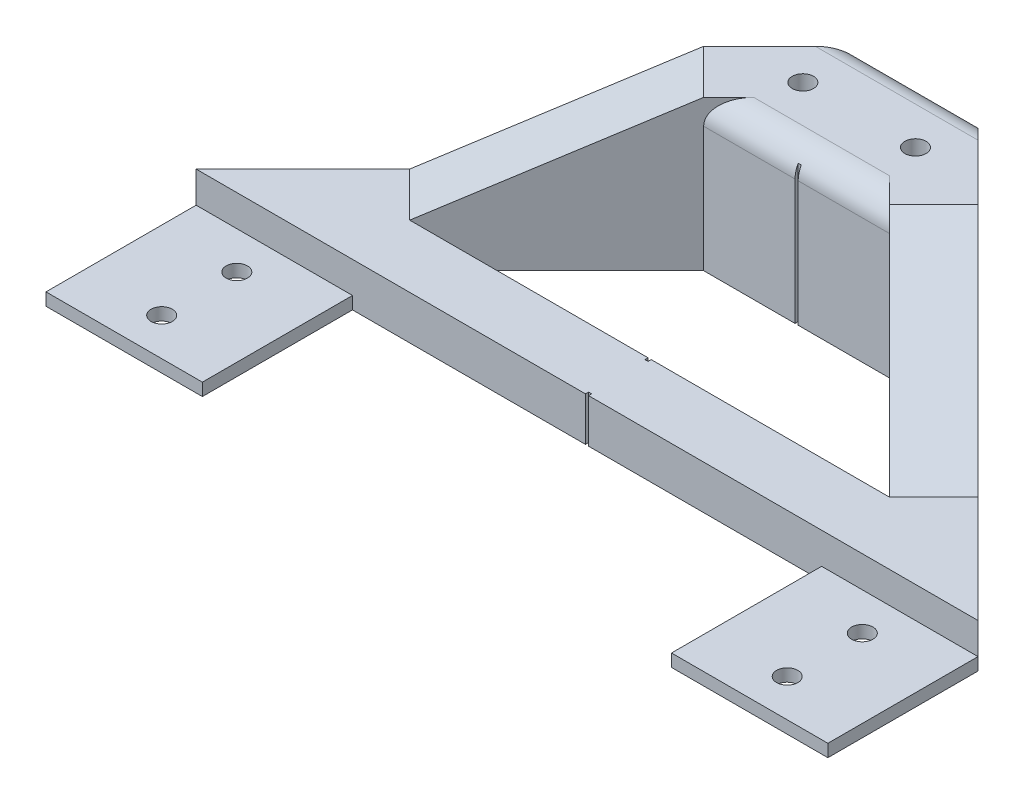
SolidWorks part; units mm, degrees
ref_plane "Front Plane" through (0, 0, 0) normal (0, 0, 1) x (1, 0, 0)
ref_plane "Top Plane" through (0, 0, 0) normal (0, 1, 0) x (1, 0, 0)
ref_plane "Right Plane" through (0, 0, 0) normal (1, 0, 0) x (0, 0, -1)
sketch "Triangle" plane through (0, 0, 0) normal (0, 1, 0) x (1, 0, 0)
  line L0 (0, 0) -> (125, 0)
  line L1 (125, 0) -> (71.5, 53.5)
  line L2 (53.5, 53.5) -> (0, 0)
  line L3 (62.5, 0) -> (62.5, 53.5) construction
  line L4 (53.5, 53.5) -> (71.5, 53.5)
  line L5 (24.1421, 10) -> (100.8579, 10)
  line L6 (100.8579, 10) -> (77.3579, 33.5)
  line L7 (77.3579, 33.5) -> (47.6421, 33.5)
  line L8 (47.6421, 33.5) -> (24.1421, 10)
  dimension "D1" = 125
  dimension "D2" = 20
  dimension "D3" = 45
  dimension "D4" = 45
  dimension "D5" = 10
  dimension "D6" = 18
  dimension "D7" = 10
  dimension "D8" = 45
  dimension "D9" = 10
  dimension "D10" = 45
sketch "Bearing Mounts" plane through (0, 0, 0) normal (0, 1, 0) x (1, 0, 0)
  line L0 (12.5, -24) -> (12.5, 0) construction
  line L1 (25, 0) -> (0, 0)
  line L2 (25, 0) -> (25, -24)
  line L3 (25, -24) -> (0, -24)
  line L4 (0, 0) -> (0, -24)
  line L5 (112.5, -24) -> (112.5, 0) construction
  line L6 (125, 0) -> (100, 0)
  line L7 (125, 0) -> (125, -24)
  line L8 (125, -24) -> (100, -24)
  line L9 (100, 0) -> (100, -24)
  line L10 (100, -24) -> (25, -24) construction
  line L11 (62.5, -24) -> (62.5, 68.4083) construction
  line L14 (62.5, 53.5) -> (62.5, -51.9511) construction
  dimension "D1" = 24
  dimension "D2" = 25
  dimension "D3" = 24
  dimension "D4" = 25
  dimension "D5" = 100
extrude "Bearing Mount Plates" add sketch "Bearing Mounts" along normal blind 2
extrude "Bridge" add sketch "Triangle" along normal blind 7
sketch "M3 Bearing Holes" plane through (0, 0, 0) normal (0, -1, 0) x (1, 0, 0)
  line L0 (125, 24) -> (125, 0) construction
  line L2 (125, 0) -> (71.5, -53.5) construction
  line L4 (100, 0) -> (100, 24) construction
  line L5 (0, 24) -> (25, 24) construction
  line L6 (0, 0) -> (125, 0) construction
  line L7 (25, 24) -> (25, 0) construction
  line L12 (100, 24) -> (125, 24) construction
  circle A0 centre (112.5, 6) radius 1.7
  circle A1 centre (112.5, 18) radius 1.7
  circle A2 centre (12.5, 6) radius 1.7
  circle A3 centre (12.5, 18) radius 1.7
  dimension "D1" = 3.4
  dimension "D5" = 6
  dimension "D10" = 3.4
  dimension "D2" = 6
  dimension "D3" = 12.5
  dimension "D4" = 6
  dimension "D6" = 12.5
  dimension "D7" = 12.5
  dimension "D8" = 6
  dimension "D9" = 12.5
extrude "Bearing Mount Holes" cut sketch "M3 Bearing Holes" against normal up to surface (2 mm away) up to face at (12.5, 2, 12)
sketch "Sketch7" plane through (0, 0, 0) normal (0, 0, 1) x (1, 0, 0)
  line L0 (62.5, 0) -> (62.5, 7)
  line L1 (0, 7) -> (125, 7) construction
  line L2 (24.1421, 0) -> (100.8579, 0) construction
  line L3 (62.25, 7) -> (62.75, 7)
  line L4 (62.25, 7) -> (62.25, 0)
  line L5 (62.25, 0) -> (62.75, 0)
  line L6 (62.75, 7) -> (62.75, 0)
  dimension "D1" = 0.25
  dimension "D2" = 0.25
extrude "Alignment helper 1" cut sketch "Sketch7" against normal blind 0.5 contours L4 L5 L6 L3
sketch "Sketch24" plane through (0, 0, 0) normal (0, -1, 0) x (1, 0, 0)
  line L0 (100.8579, -10) -> (24.1421, -10) construction
  line L2 (62.75, -10.5) -> (62.25, -10.5)
  line L3 (62.75, -10.5) -> (62.75, -9.5)
  line L4 (62.75, -9.5) -> (62.25, -9.5)
  line L5 (62.25, -10.5) -> (62.25, -9.5)
  line L6 (62.75, -10.5) -> (62.25, -9.5) construction
  line L7 (62.75, -9.5) -> (62.25, -10.5) construction
  point P4 (62.5, -10)
  dimension "D1" = 0.5
  dimension "D2" = 1
extrude "Alignment helper 1b" cut sketch "Sketch24" against normal blind 10
sketch "Sketch9" plane through (0, 7, 0) normal (0, 1, 0) x (1, 0, 0)
  line L0 (33.5, 33.5) -> (53.5, 53.5)
  line L1 (125, 0) -> (71.5, 53.5) construction
  line L2 (91.5, 33.5) -> (33.5, 33.5)
  line L3 (53.5, 53.5) -> (0, 0) construction
  line L4 (53.5, 53.5) -> (71.5, 53.5)
  line L5 (71.5, 53.5) -> (91.5, 33.5)
extrude "Belt Mount" add sketch "Sketch9" along normal blind 17
sketch "Sketch8" plane through (0, 0, 0) normal (0, 1, 0) x (1, 0, 0)
  circle A0 centre (53.5, 43.5) radius 1.7
  circle A1 centre (71.5, 43.5) radius 1.7
  dimension "D1" = 3.4
  dimension "D2" = 3.4
  dimension "D3" = 18
  dimension "D4" = 10
extrude "Belt Mount Holes" cut sketch "Sketch8" along normal through all contours A0 | A1
sketch "Sketch14" plane through (0, 7, 0) normal (0, 1, 0) x (1, 0, 0)
  line L0 (24.1421, 10) -> (47.6421, 33.5)
  line L1 (47.6421, 33.5) -> (33.5, 33.5)
  line L2 (33.5, 33.5) -> (10, 10)
  line L3 (33.5, 33.5) -> (0, 0) construction
  line L4 (10, 10) -> (24.1421, 10)
extrude "Angle Left" add sketch "Sketch14" along normal blind 17
sketch "Sketch17" plane through (7.0711, 0, 7.0711) normal (0.7071, 0, 0.7071) x (0.7071, 0, -0.7071)
  line L0 (57.3762, 24) -> (24.1421, 7)
  line L2 (0, 7) -> (44.0174, 7) construction
  line L3 (24.1421, 24) -> (57.3762, 24)
  line L4 (24.1421, 7) -> (10, 7)
  line L5 (10, 7) -> (10, 24)
  line L6 (10, 24) -> (24.1421, 24)
extrude "Angle Left Cut" cut sketch "Sketch17" against normal blind 30
sketch "Sketch20" plane through (0, 7, 0) normal (0, 1, 0) x (1, 0, 0)
  line L0 (100.8579, 10) -> (115, 10)
  line L1 (125, 0) -> (71.5, 53.5) construction
  line L2 (115, 10) -> (91.5, 33.5)
  line L3 (91.5, 33.5) -> (77.3579, 33.5)
  line L4 (77.3579, 33.5) -> (100.8579, 10)
extrude "Angle Right" add sketch "Sketch20" along normal blind 17
sketch "Sketch21" plane through (55.4289, 0, -55.4289) normal (-0.7071, 0, 0.7071) x (0.7071, 0, 0.7071)
  line L0 (31.0122, 24) -> (64.2462, 7)
  line L2 (64.2462, 24) -> (31.0122, 24)
  line L3 (64.2462, 7) -> (78.3883, 7)
  line L4 (78.3883, 7) -> (78.3883, 24)
  line L5 (78.3883, 24) -> (64.2462, 24)
  line L6 (44.371, 7) -> (88.3883, 7) construction
extrude "Angle Right Cut" cut sketch "Sketch21" against normal blind 30
sketch "Sketch23" plane through (0, 0, 0) normal (0, 1, 0) x (1, 0, 0)
  line L1 (62.75, 53) -> (62.25, 53)
  line L2 (62.75, 53) -> (62.75, 54)
  line L3 (62.75, 54) -> (62.25, 54)
  line L4 (62.25, 53) -> (62.25, 54)
  line L5 (62.75, 53) -> (62.25, 54) construction
  line L6 (62.75, 54) -> (62.25, 53) construction
  point P0 (62.5, 53.5)
  dimension "D1" = 0.5
  dimension "D2" = 1
extrude "Alignment helper 2" cut sketch "Sketch23" along normal through all
fillet "Fillet5" radius 4 1 edges at (62.5, 24, -33.5) type face fillet first side face at (62.5, 18, -33.5) second side face at (71.5, 24, -41.8)
fillet "Fillet2" radius 4 2 edges at (67.125, 24, -53.5) (57.875, 24, -53.5) type face fillet first side face at (57.875, 12, -53.5) first side face at (67.125, 12, -53.5) second side face at (71.5, 24, -41.8)
sketch "Sketch25" plane through (0, 0, 0) normal (0, -1, 0) x (1, 0, 0)
  line L0 (47.6421, -33.5) -> (77.3579, -33.5) construction
  line L2 (62.75, -33) -> (62.25, -33)
  line L3 (62.75, -33) -> (62.75, -34)
  line L4 (62.75, -34) -> (62.25, -34)
  line L5 (62.25, -33) -> (62.25, -34)
  line L6 (62.75, -33) -> (62.25, -34) construction
  line L7 (62.75, -34) -> (62.25, -33) construction
  point P4 (62.5, -33.5)
  dimension "D1" = 0.5
  dimension "D2" = 1
extrude "Alignment helper 2b" cut sketch "Sketch25" against normal through all
